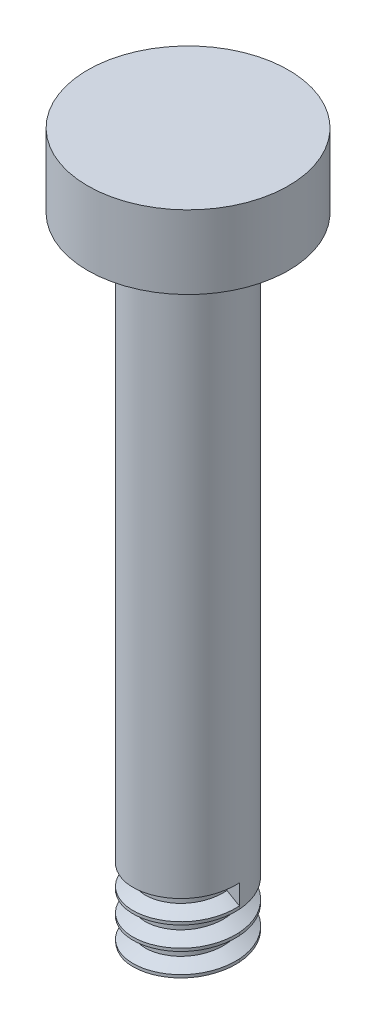
SolidWorks part; units mm, degrees
material "6061-T6 (SS)"
ref_plane "Front" through (0, 0, 0) normal (0, 0, 1) x (1, 0, 0)
ref_plane "Top" through (0, 0, 0) normal (0, 1, 0) x (1, 0, 0)
ref_plane "Right" through (0, 0, 0) normal (1, 0, 0) x (0, 0, -1)
sketch "Sketch2" plane through (0, 0, 0) normal (0, 1, 0) x (1, 0, 0)
  circle A0 centre (0, 0) radius 1.4224
  dimension "D1" = 2.8448
extrude "Boss-Extrude1" add sketch "Sketch2" along normal blind 17.4625
sketch "Sketch6" plane through (0, 17.4625, 0) normal (0, 1, 0) x (1, 0, 0)
  circle A0 centre (0, 0) radius 2.7813
extrude "Boss-Extrude2" add sketch "Sketch6" along normal blind 2.032
thread "Thread2" pitch 0.635 method cut profile "Thread Profile2" start angle 0, offset 1, length 0, pitch 0.635, diameter 2.8448
ref_plane "Plane2" through (1.4224, -1, 0) normal (0, 0, 1) x (1, 0, 0)
sketch "Thread Profile2" plane through (1.4224, -1, 0) normal (0, 0, 1) x (1, 0, 0)
  line L0 (0, 0) -> (0, 0.635) construction
  line L11 (0, 0) -> (0, 0.5556)
  line L12 (0, 0.5556) -> (-0.3437, 0.3572)
  line L13 (-0.3437, 0.3572) -> (-0.3437, 0.1984)
  line L15 (-0.3437, 0.1984) -> (0, 0)
  line L17 (-0.3437, 0.2778) -> (0, 0.2778) construction
  point P2 (0, 0)
  dimension "Pitch" = 0.635
  dimension "Profile_Angle" = 60
  dimension "Profile_Land" = 0.1588
  dimension "Profile_Height" = 0.3437
